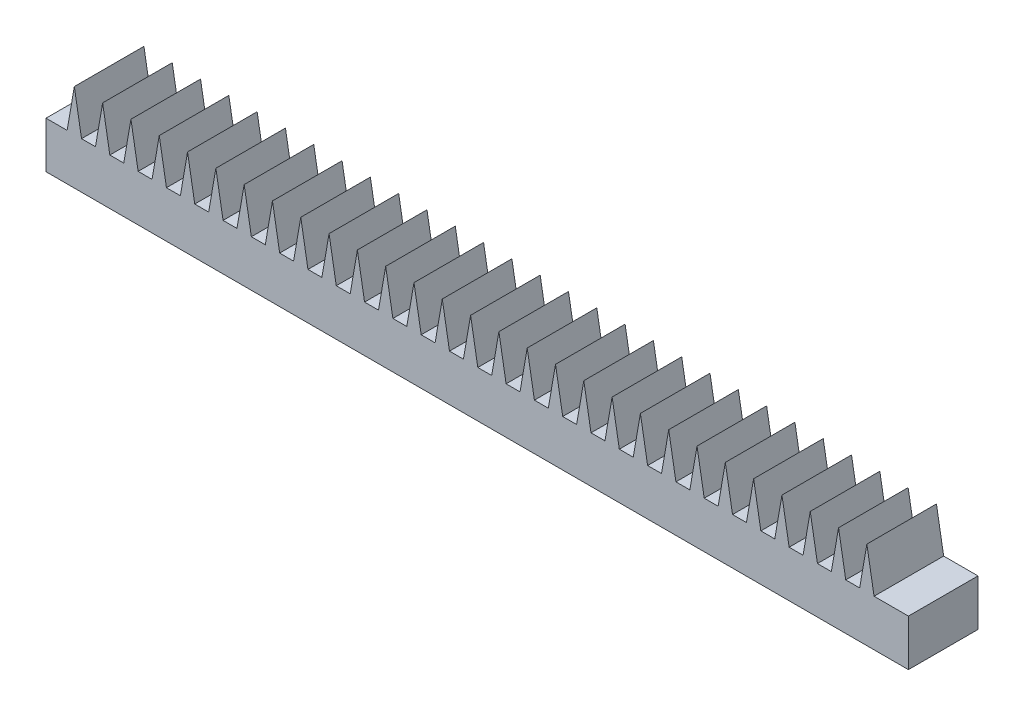
SolidWorks part; units mm, degrees
ref_plane "Front Plane" through (0, 0, 0) normal (0, 0, 1) x (1, 0, 0)
ref_plane "Top Plane" through (0, 0, 0) normal (0, 1, 0) x (1, 0, 0)
ref_plane "Right Plane" through (0, 0, 0) normal (1, 0, 0) x (0, 0, -1)
sketch "Sketch1" plane through (0, 0, 0) normal (0, 0, 1) x (1, 0, 0)
  line L2 (-9.6198, 0) -> (-9.3198, 0)
  line L3 (-9.3198, 0) -> (-9.1648, 0.8961)
  line L4 (8.3702, 0) -> (8.8106, 0)
  line L5 (-8.7098, 0) -> (-8.5548, 0.8961)
  line L6 (-9.0098, 0) -> (-8.7098, 0)
  line L7 (-9.0098, 0) -> (-9.1648, 0.8961)
  line L8 (-8.0998, 0) -> (-7.9448, 0.8961)
  line L9 (-8.3998, 0) -> (-8.0998, 0)
  line L10 (-8.3998, 0) -> (-8.5548, 0.8961)
  line L11 (-7.4898, 0) -> (-7.3348, 0.8961)
  line L12 (-7.7898, 0) -> (-7.4898, 0)
  line L13 (-7.7898, 0) -> (-7.9448, 0.8961)
  line L14 (-6.8798, 0) -> (-6.7248, 0.8961)
  line L15 (-7.1798, 0) -> (-6.8798, 0)
  line L16 (-7.1798, 0) -> (-7.3348, 0.8961)
  line L17 (-6.2698, 0) -> (-6.1148, 0.8961)
  line L18 (-6.5698, 0) -> (-6.2698, 0)
  line L19 (-6.5698, 0) -> (-6.7248, 0.8961)
  line L20 (-5.6598, 0) -> (-5.5048, 0.8961)
  line L21 (-5.9598, 0) -> (-5.6598, 0)
  line L22 (-5.9598, 0) -> (-6.1148, 0.8961)
  line L23 (-5.0498, 0) -> (-4.8948, 0.8961)
  line L24 (-5.3498, 0) -> (-5.0498, 0)
  line L25 (-5.3498, 0) -> (-5.5048, 0.8961)
  line L26 (-4.4398, 0) -> (-4.2848, 0.8961)
  line L27 (-4.7398, 0) -> (-4.4398, 0)
  line L28 (-4.7398, 0) -> (-4.8948, 0.8961)
  line L29 (-3.8298, 0) -> (-3.6748, 0.8961)
  line L30 (-4.1298, 0) -> (-3.8298, 0)
  line L31 (-4.1298, 0) -> (-4.2848, 0.8961)
  line L32 (-3.2198, 0) -> (-3.0648, 0.8961)
  line L33 (-3.5198, 0) -> (-3.2198, 0)
  line L34 (-3.5198, 0) -> (-3.6748, 0.8961)
  line L35 (-2.6098, 0) -> (-2.4548, 0.8961)
  line L36 (-2.9098, 0) -> (-2.6098, 0)
  line L37 (-2.9098, 0) -> (-3.0648, 0.8961)
  line L38 (-1.9998, 0) -> (-1.8448, 0.8961)
  line L39 (-2.2998, 0) -> (-1.9998, 0)
  line L40 (-2.2998, 0) -> (-2.4548, 0.8961)
  line L41 (-1.3898, 0) -> (-1.2348, 0.8961)
  line L42 (-1.6898, 0) -> (-1.3898, 0)
  line L43 (-1.6898, 0) -> (-1.8448, 0.8961)
  line L44 (-0.7798, 0) -> (-0.6248, 0.8961)
  line L45 (-1.0798, 0) -> (-0.7798, 0)
  line L46 (-1.0798, 0) -> (-1.2348, 0.8961)
  line L47 (-0.1698, 0) -> (-0.0148, 0.8961)
  line L48 (-0.4698, 0) -> (-0.1698, 0)
  line L49 (-0.4698, 0) -> (-0.6248, 0.8961)
  line L50 (0.4402, 0) -> (0.5952, 0.8961)
  line L51 (0.1402, 0) -> (0.4402, 0)
  line L52 (0.1402, 0) -> (-0.0148, 0.8961)
  line L53 (1.0502, 0) -> (1.2052, 0.8961)
  line L54 (0.7502, 0) -> (1.0502, 0)
  line L55 (0.7502, 0) -> (0.5952, 0.8961)
  line L56 (1.6602, 0) -> (1.8152, 0.8961)
  line L57 (1.3602, 0) -> (1.6602, 0)
  line L58 (1.3602, 0) -> (1.2052, 0.8961)
  line L59 (2.2702, 0) -> (2.4252, 0.8961)
  line L60 (1.9702, 0) -> (2.2702, 0)
  line L61 (1.9702, 0) -> (1.8152, 0.8961)
  line L62 (2.8802, 0) -> (3.0352, 0.8961)
  line L63 (2.5802, 0) -> (2.8802, 0)
  line L64 (2.5802, 0) -> (2.4252, 0.8961)
  line L65 (3.4902, 0) -> (3.6452, 0.8961)
  line L66 (3.1902, 0) -> (3.4902, 0)
  line L67 (3.1902, 0) -> (3.0352, 0.8961)
  line L68 (4.1002, 0) -> (4.2552, 0.8961)
  line L69 (3.8002, 0) -> (4.1002, 0)
  line L70 (3.8002, 0) -> (3.6452, 0.8961)
  line L71 (4.7102, 0) -> (4.8652, 0.8961)
  line L72 (4.4102, 0) -> (4.7102, 0)
  line L73 (4.4102, 0) -> (4.2552, 0.8961)
  line L74 (5.3202, 0) -> (5.4752, 0.8961)
  line L75 (5.0202, 0) -> (5.3202, 0)
  line L76 (5.0202, 0) -> (4.8652, 0.8961)
  line L77 (5.9302, 0) -> (6.0852, 0.8961)
  line L78 (5.6302, 0) -> (5.9302, 0)
  line L79 (5.6302, 0) -> (5.4752, 0.8961)
  line L80 (6.5402, 0) -> (6.6952, 0.8961)
  line L81 (6.2402, 0) -> (6.5402, 0)
  line L82 (6.2402, 0) -> (6.0852, 0.8961)
  line L83 (7.1502, 0) -> (7.3052, 0.8961)
  line L84 (6.8502, 0) -> (7.1502, 0)
  line L85 (6.8502, 0) -> (6.6952, 0.8961)
  line L86 (7.7602, 0) -> (7.9152, 0.8961)
  line L87 (7.4602, 0) -> (7.7602, 0)
  line L88 (7.4602, 0) -> (7.3052, 0.8961)
  line L89 (8.8106, 0) -> (8.8106, -1)
  line L90 (8.0702, 0) -> (8.3702, 0)
  line L91 (8.0702, 0) -> (7.9152, 0.8961)
  line L92 (-9.7755, 0) -> (-9.7755, -1)
  line L93 (-9.7755, -1) -> (8.8106, -1)
  line L94 (-9.6198, 0) -> (-9.7755, 0)
  line L96 (8.3702, 0) -> (8.5258, 0.9) [skipped]
  point P4 (0, 0)
  point P9 (-9.4698, 0)
  dimension "D2" = 0.3
  dimension "D3" = 1
  dimension "D4" = 30
extrude "Boss-Extrude1" add sketch "Sketch1" along normal blind 1.5
